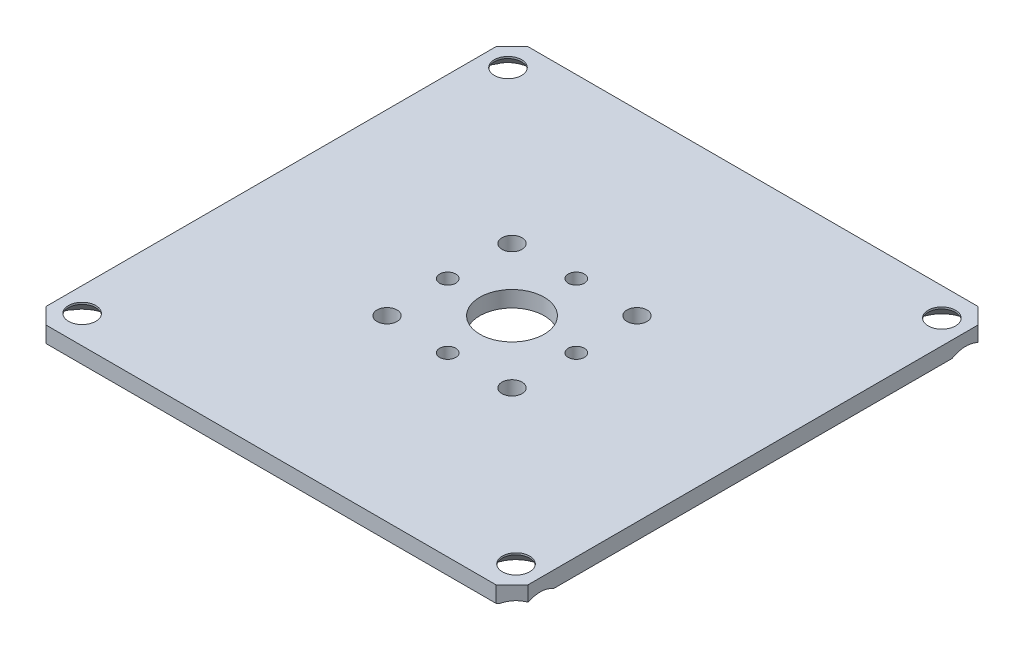
SolidWorks part; units mm, degrees
material "1060 Alloy"
ref_plane "Front Plane" through (0, 0, 0) normal (0, 0, 1) x (1, 0, 0)
ref_plane "Top Plane" through (0, 0, 0) normal (0, 1, 0) x (1, 0, 0)
ref_plane "Right Plane" through (0, 0, 0) normal (1, 0, 0) x (0, 0, -1)
sketch "Sketch1" plane through (0, 0, 0) normal (0, 0, 1) x (1, 0, 0)
  line L0 (-30, 0) -> (30, 0)
  line L1 (0, 0) -> (0, 13.1388) construction
  dimension "D1" = 60
sheet metal parameters "Sheet-Metal1" thickness 2 parameters "D1"=2
base flange "Base-Flange1" sketch "Sketch1" end condition blind depth 60 reverse direction no thickness 2 reverse thickness direction no bend radius 2
sketch "Sketch2" plane through (0, 0, 0) normal (0, 1, 0) x (1, 0, 0)
  line L0 (0, -3.5) -> (0, 0) construction
  line L1 (-27, -3.5) -> (27, -3.5) construction
  line L2 (-27, -3.5) -> (-27, -56.5) construction
  line L3 (-27, -56.5) -> (27, -56.5) construction
  line L4 (27, -3.5) -> (27, -56.5) construction
  line L5 (-27, -30) -> (-30, -30) construction
  line L7 (-30, -60) -> (-30, 0) construction
  circle A0 centre (-27, -3.5) radius 1.25
  circle A1 centre (-27, -56.5) radius 1.25
  circle A2 centre (27, -56.5) radius 1.25
  circle A3 centre (27, -3.5) radius 1.25
  dimension "D1" = 2.5
  dimension "D2" = 54
  dimension "D3" = 53
extrude "Cut-Extrude1" cut sketch "Sketch2" against normal blind 10 normal cut yes
hole_wizard "CSK for M3 Hex Socket Countersunk Head Screw1" positions "3DSketch1" profile "Sketch3" countersink size "M3" standard "DIN" end condition through all
sketch3d "3DSketch1"
  line L0 (27, -2, 3.5) -> (27, 0, 3.5) construction
  line L1 (-27, -2, 3.5) -> (-27, 0, 3.5) construction
  line L2 (27, -2, 56.5) -> (27, 0, 56.5) construction
  line L3 (-27, -2, 56.5) -> (-27, 0, 56.5) construction
  point P0 (27, -2, 3.5)
  point P4 (-27, -2, 3.5)
  point P8 (27, -2, 56.5)
  point P12 (-27, -2, 56.5)
sketch "Sketch3" plane through (27, -2, 3.5) normal (1, 0, 0) x (0, 0, -1)
  line L0 (0, 0) -> (0, 2)
  line L1 (0, 2) -> (1.7, 2)
  line L2 (1.7, 2) -> (1.7, 1.77)
  line L3 (1.7, 1.77) -> (3.47, 0)
  line L5 (3.47, 0) -> (0, 0)
  line L6 (-1.7, 1.77) -> (-3.47, 0) construction
  line L11 (0, -6.35) -> (0, 107.95) construction
  dimension "Thru Hole Dia." = 3.4
  dimension "Thru Hole Depth" = 2
  dimension "Near C'Sink Dia." = 6.94
  dimension "Near C'Sink Angle" = 90
sketch "Sketch4" plane through (0, 0, 0) normal (0, 1, 0) x (1, 0, 0)
  line L0 (-30, 0) -> (30, -60) construction
  circle A0 centre (0, -30) radius 4
  dimension "D1" = 8
extrude "Cut-Extrude2" cut sketch "Sketch4" against normal up to next normal cut yes
chamfer "Chamfer1" distance 2 angle 45 4 edges at (30, -1, 0) (30, -1, 60) (-30, -1, 60) (-30, -1, 0)
sketch "Sketch5" plane through (0, -2, 0) normal (0, -1, 0) x (1, 0, 0)
  circle A0 centre (7.7782, 37.7782) radius 1.25
  circle A1 centre (-7.7782, 37.7782) radius 1.25
  circle A2 centre (-7.7782, 22.2218) radius 1.25
  circle A3 centre (7.7782, 22.2218) radius 1.25
  circle A4 centre (8, 30) radius 1
  circle A5 centre (0, 22) radius 1
  circle A6 centre (-8, 30) radius 1
  circle A7 centre (0, 38) radius 1
  dimension "D1" = 2
  dimension "D2" = 2.5
extrude "Cut-Extrude3" cut sketch "Sketch5" against normal up to next normal cut yes
flat pattern "Flat-Pattern1" [suppressed]
sketch "Bend-Lines1" plane through (0, 0, 0) normal (0, 1, 0) x (-1, 0, 0)
